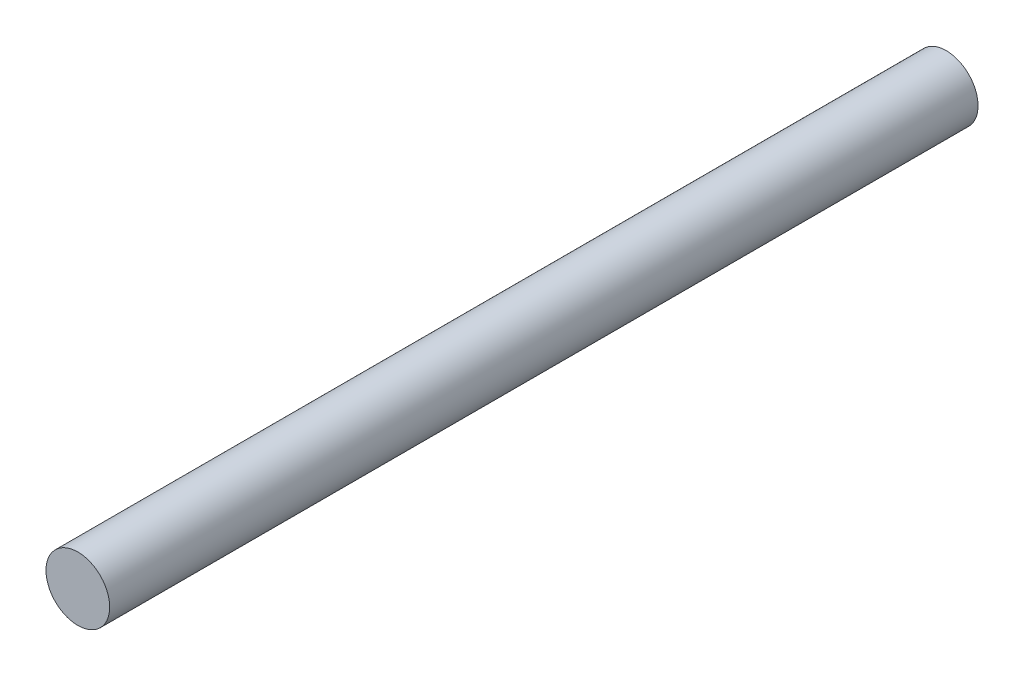
SolidWorks part; units mm, degrees
ref_plane "Front Plane" through (0, 0, 0) normal (0, 0, 1) x (1, 0, 0)
ref_plane "Top Plane" through (0, 0, 0) normal (0, 1, 0) x (1, 0, 0)
ref_plane "Right Plane" through (0, 0, 0) normal (1, 0, 0) x (0, 0, -1)
sketch "Sketch1" plane through (0, 0, 0) normal (0, 0, 1) x (1, 0, 0)
  circle A0 centre (0, 0) radius 3.3
  dimension "D1" = 6.6
extrude "Boss-Extrude1" add sketch "Sketch1" along normal blind 90
ref_axis "Axis1" through (0, 0, 90) along (0, 0, -1)
